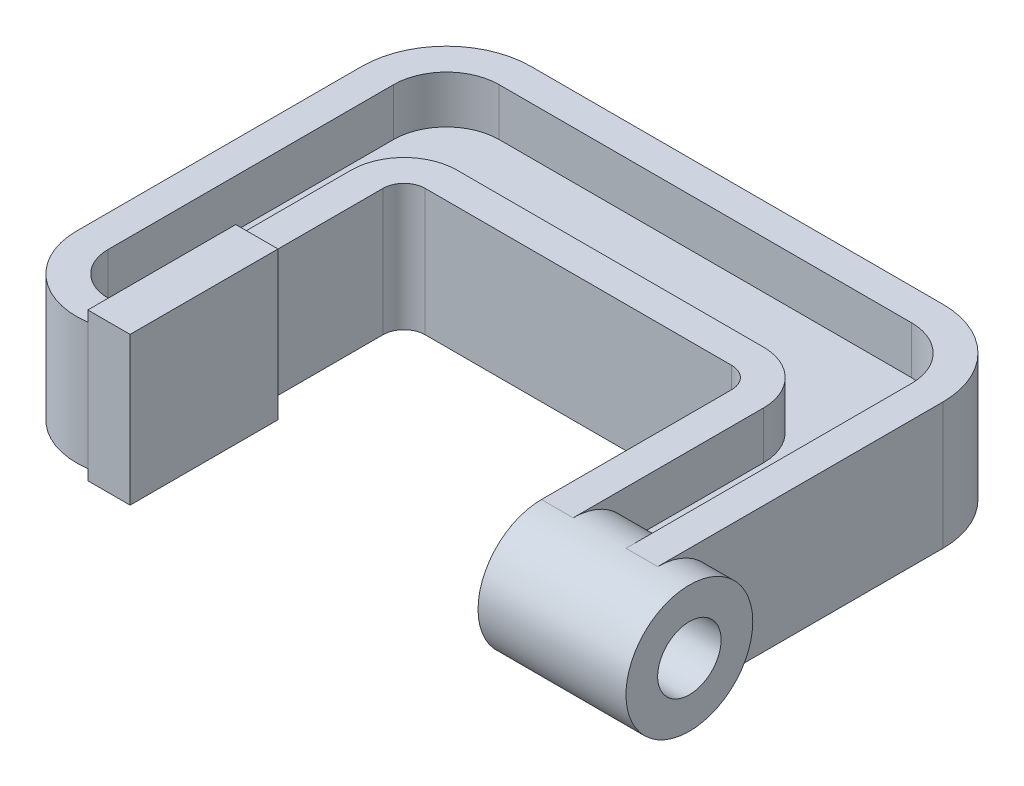
SolidWorks part; units mm, degrees
note: The reader was unsure of these and kept them because the rebuilt part matched: shared geometry of "Sketch1<4>".
ref_plane "Front Plane" through (0, 0, 0) normal (0, 0, 1) x (1, 0, 0)
ref_plane "Top Plane" through (0, 0, 0) normal (0, 1, 0) x (1, 0, 0)
ref_plane "Right Plane" through (0, 0, 0) normal (1, 0, 0) x (0, 0, -1)
sketch "Sketch1" plane through (0, 0, 0) normal (0, 1, 0) x (1, 0, 0)
  line L0 (0, 0) -> (0, 108)
  line L1 (32, 140) -> (188, 140)
  line L2 (220, 108) -> (220, 0)
  line L3 (44, 0) -> (44, 72)
  line L4 (52, 80) -> (168, 80)
  line L5 (176, 72) -> (176, 0)
  line L6 (32, 0) -> (32, 72)
  line L7 (52, 92) -> (168, 92)
  line L8 (188, 72) -> (188, 0)
  line L9 (12, 0) -> (12, 108)
  line L10 (32, 128) -> (188, 128)
  line L11 (208, 108) -> (208, 0)
  line L12 (32, 0) -> (48, 0)
  line L13 (48, 0) -> (48, -28)
  line L14 (48, -28) -> (32, -28)
  line L15 (32, -28) -> (32, 0)
  line L16 (176, 0) -> (188, 0)
  line L17 (188, 0) -> (208, 0)
  line L18 (208, 0) -> (220, 0)
  arc A0 (0, 108) -> (32, 140) centre (32, 108) cw
  arc A1 (188, 140) -> (220, 108) centre (188, 108) cw
  arc A2 (44, 72) -> (52, 80) centre (52, 72) cw
  arc A3 (168, 80) -> (176, 72) centre (168, 72) cw
  arc A4 (32, 72) -> (52, 92) centre (52, 72) cw
  arc A5 (168, 92) -> (188, 72) centre (168, 72) cw
  arc A6 (12, 108) -> (32, 128) centre (32, 108) cw
  arc A7 (188, 128) -> (208, 108) centre (188, 108) cw
  arc A8 (0, 0) -> (32, -27.7128) centre (28, 0) ccw
  arc A9 (12, 0) -> (32, -15.4919) centre (28, 0) ccw
  point P16 (0, 140)
  point P19 (220, 140)
  point P22 (44, 80)
  point P25 (176, 80)
  dimension "D6" = 32
  dimension "D7" = 32
  dimension "D8" = 8
  dimension "D9" = 8
  dimension "D14" = 28
  dimension "D15" = 16
  dimension "D1" = 140
  dimension "D2" = 220
  dimension "D3" = 80
  dimension "D4" = 132
  dimension "D5" = 44
  dimension "D12" = 28
  dimension "D13" = 16
  dimension "D10" = 12
  dimension "D11" = 12
extrude "Boss-Extrude2" add sketch "Sketch1" along normal mid plane 12 contours L9 A9 L15 L6 A4 L7 A5 L8 L17 L11 A7 L10 A6
extrude "Boss-Extrude3" add sketch "Sketch1<4>" along normal mid plane 48 contours A9 L9 A6 L10 A7 L11 L18 L2 A1 L1 A0 L0 A8 L15 | A5 L7 A4 L6 L12 L3 A2 L4 A3 L5 L16 L8
sketch "Sketch1<4>" plane through (0, 0, 0) normal (0, 1, 0) x (1, 0, 0) same geometry as "Sketch1"
sketch "Sketch4" plane through (0, 24, 0) normal (0, 1, 0) x (1, 0, 0)
  line L1 (32, -27.7128) -> (48, -27.7128)
  line L2 (32, -27.7128) -> (32, 28.2872)
  line L3 (32, 28.2872) -> (48, 28.2872)
  line L4 (48, -27.7128) -> (48, 28.2872)
  dimension "D1" = 16
  dimension "D2" = 56
sketch "Sketch7" plane through (220, 0, 0) normal (1, 0, 0) x (0, 0, -1)
  circle A0 centre (0, 0) radius 24
  dimension "D1" = 48
extrude "Boss-Extrude5" add sketch "Sketch7" against normal blind 56 from offset 12
extrude "Boss-Extrude6" add sketch "Sketch4" against normal blind 56 from offset 4
hole_wizard "M24 Clearance Slot4" positions "Sketch26" profile "Sketch27" size "M24" standard "ISO"
sketch "Sketch26" plane through (232, 0, 0) normal (1, 0, 0) x (0, 0, -1)
  point P0 (0, 0)
sketch "Sketch27" plane through (232, 0, 0) normal (0, 1, 0) x (0, 0, -1)
  line L0 (0, 0) -> (0, 56)
  line L1 (0, 56) -> (12, 56)
  line L2 (12, 56) -> (12, 0)
  line L5 (12, 0) -> (0, 0)
  line L11 (0, -6.35) -> (0, 107.95) construction
  dimension "Thru Hole Dia." = 24
  dimension "Thru Hole Depth" = 56
cosmetic thread "Cosmetic Thread2" parameters "D2"=24
